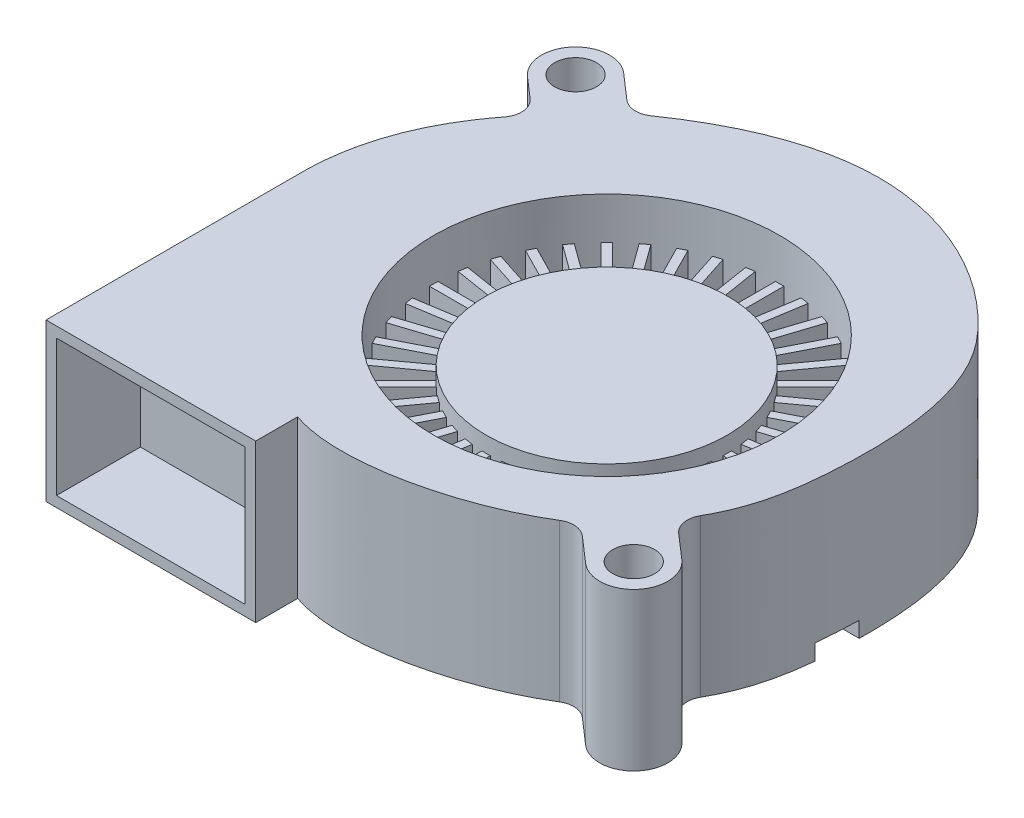
SolidWorks part; units mm, degrees
ref_plane "Front Plane" through (0, 0, 0) normal (0, 0, 1) x (1, 0, 0)
ref_plane "Top Plane" through (0, 0, 0) normal (0, 1, 0) x (1, 0, 0)
ref_plane "Right Plane" through (0, 0, 0) normal (1, 0, 0) x (0, 0, -1)
sketch "Sketch1" plane through (0, 0, 0) normal (0, 1, 0) x (1, 0, 0)
  line L0 (0, 53.1722) -> (0, -73.3303) construction
  line L1 (-85.9264, 74.8353) -> (113.2192, -98.6052) construction
  line L2 (0, 0) -> (35.3553, 35.3553) construction
  line L3 (-92.8119, -25.4688) -> (115.0441, -25.4688) construction
  line L4 (-28, -25.4688) -> (-8, -25.4688)
  line L5 (-8, -25.4688) -> (-8, -21.4688)
  line L6 (-28, -25.4688) -> (-28, -0.4688)
  line L7 (-25.1345, 17.5804) -> (-21.7087, 14.5968)
  line L8 (-27.6468, 14.6958) -> (-16.0044, 28.0636) construction
  line L9 (-20.8655, 22.482) -> (-17.254, 19.3367)
  line L10 (15.2709, -22.8153) -> (26.2326, -10.229) construction
  line L11 (17.8491, -19.855) -> (14.2534, -16.7234)
  line L12 (22.1181, -14.9534) -> (18.496, -11.7988)
  line L13 (5.1229, 26) -> (-4.8978, 26) construction
  circle A0 centre (0, 0) radius 11.5
  circle A1 centre (0, 0) radius 16.5
  circle A2 centre (-23, 20.0312) radius 2
  circle A3 centre (19.9836, -17.4042) radius 2
  arc A4 (-20.8655, 22.482) -> (-25.1345, 17.5804) centre (-23, 20.0312) ccw
  arc A5 (17.8491, -19.855) -> (22.1181, -14.9534) centre (19.9836, -17.4042) ccw
  spline S0 degree 2 poles (-28, -0.4688) (-27.7498, 7.7362) (-21.7087, 14.5968) knots 0 0 0 0.146641 0.146641 0.146641
  spline S1 degree 3 poles (-17.254, 19.3367) (-13.1006, 22.4583) (-6.5843, 25.9822) (5.2341, 26.0653) (12.9163, 22.9052) (21.8609, 13.2015) (22.5883, 0.0872) (21.0626, -8.1071) (18.496, -11.7988) knots 0.198948 0.198948 0.198948 0.198948 0.358848 0.392677 0.521173 0.55031 0.667984 0.765326 0.765326 0.765326 0.765326
  spline S2 degree 3 poles (14.2534, -16.7234) (8.3416, -20.9384) (-2.1416, -23.5492) (-8, -21.4688) knots 0.819888 0.819888 0.819888 0.819888 1 1 1 1
  point P8 (-23, 20.0312)
  point P9 (19.9836, -17.4042)
  point P18 (-19.6066, 17.0758)
  point P21 (0, 26)
  point P22 (16.5902, -14.4488)
  point P23 (17.6777, 17.6777)
  point P25 (0, -22)
  point P27 (22, 0)
  point P32 (-20.8655, 22.482)
  point P36 (-25.1345, 17.5804)
  dimension "D1" = 23
  dimension "D2" = 33
  dimension "D5" = 26.5
  dimension "D11" = 4
  dimension "D19" = 6.5
  dimension "D21" = 6.5
  dimension "D4" = 30.5
  dimension "D7" = 8
  dimension "D8" = 20
  dimension "D9" = 4
  dimension "D10" = 25
  dimension "D12" = 26
  dimension "D13" = 26
  dimension "D14" = 22
  dimension "D15" = 45
  dimension "D16" = 25
  dimension "D17" = 22
  dimension "D18" = 22
  dimension "D22" = 5
  dimension "D23" = 45.5
extrude "Boss-Extrude1" add sketch "Sketch1" along normal blind 15 contours S0 L6 L4 L5 A1 region at (-27.2738, 0, 12.9688)
extrude "Boss-Extrude2" add sketch "Sketch1<3>" along normal blind 12.5 separate body contours A0 region at (0, 0, 0)
sketch "Sketch1<3>" plane through (0, 0, 0) normal (0, 1, 0) x (1, 0, 0) same geometry as "Sketch1"
extrude "Boss-Extrude3" add sketch "Sketch1<4>" along normal blind 7 contours A1 A0 region at (-16.0333, 0, 0)
sketch "Sketch1<4>" plane through (0, 0, 0) normal (0, 1, 0) x (1, 0, 0) same geometry as "Sketch1"
sketch "Sketch2" plane through (0, 7, 0) normal (0, 1, 0) x (1, 0, 0)
  line L0 (-0.4, 11.493) -> (-0.4, 16.4952)
  line L1 (0.4, 16.4952) -> (0.4, 11.493)
  line L4 (0, 16.5) -> (0, 11.5) construction
  line L5 (2.9755, 16.2295) -> (2.193, 11.289)
  line L6 (1.4028, 11.4141) -> (2.1853, 16.3546)
  line L7 (5.4777, 15.5642) -> (3.932, 10.8069)
  line L8 (3.1711, 11.0541) -> (4.7169, 15.8114)
  line L9 (7.845, 14.5157) -> (5.5741, 10.0588)
  line L10 (4.8613, 10.422) -> (7.1322, 14.8789)
  line L11 (10.0192, 13.1097) -> (7.079, 9.063)
  line L12 (6.4318, 9.5332) -> (9.372, 13.58)
  line L13 (11.9467, 11.381) -> (8.4097, 7.844)
  line L14 (7.844, 8.4097) -> (11.381, 11.9467)
  line L15 (13.58, 9.372) -> (9.5332, 6.4318)
  line L16 (9.063, 7.079) -> (13.1097, 10.0192)
  line L17 (14.8789, 7.1322) -> (10.422, 4.8613)
  line L18 (10.0588, 5.5741) -> (14.5157, 7.845)
  line L19 (15.8114, 4.7169) -> (11.0541, 3.1711)
  line L20 (10.8069, 3.932) -> (15.5642, 5.4777)
  line L21 (16.3546, 2.1853) -> (11.4141, 1.4028)
  line L22 (11.289, 2.193) -> (16.2295, 2.9755)
  line L23 (16.4952, -0.4) -> (11.493, -0.4)
  line L24 (11.493, 0.4) -> (16.4952, 0.4)
  line L25 (16.2295, -2.9755) -> (11.289, -2.193)
  line L26 (11.4141, -1.4028) -> (16.3546, -2.1853)
  line L27 (15.5642, -5.4777) -> (10.8069, -3.932)
  line L28 (11.0541, -3.1711) -> (15.8114, -4.7169)
  line L29 (14.5157, -7.845) -> (10.0588, -5.5741)
  line L30 (10.422, -4.8613) -> (14.8789, -7.1322)
  line L31 (13.1097, -10.0192) -> (9.063, -7.079)
  line L32 (9.5332, -6.4318) -> (13.58, -9.372)
  line L33 (11.381, -11.9467) -> (7.844, -8.4097)
  line L34 (8.4097, -7.844) -> (11.9467, -11.381)
  line L35 (9.372, -13.58) -> (6.4318, -9.5332)
  line L36 (7.079, -9.063) -> (10.0192, -13.1097)
  line L37 (7.1322, -14.8789) -> (4.8613, -10.422)
  line L38 (5.5741, -10.0588) -> (7.845, -14.5157)
  line L39 (4.7169, -15.8114) -> (3.1711, -11.0541)
  line L40 (3.932, -10.8069) -> (5.4777, -15.5642)
  line L41 (2.1853, -16.3546) -> (1.4028, -11.4141)
  line L42 (2.193, -11.289) -> (2.9755, -16.2295)
  line L43 (-0.4, -16.4952) -> (-0.4, -11.493)
  line L44 (0.4, -11.493) -> (0.4, -16.4952)
  line L45 (-2.9755, -16.2295) -> (-2.193, -11.289)
  line L46 (-1.4028, -11.4141) -> (-2.1853, -16.3546)
  line L47 (-5.4777, -15.5642) -> (-3.932, -10.8069)
  line L48 (-3.1711, -11.0541) -> (-4.7169, -15.8114)
  line L49 (-7.845, -14.5157) -> (-5.5741, -10.0588)
  line L50 (-4.8613, -10.422) -> (-7.1322, -14.8789)
  line L51 (-10.0192, -13.1097) -> (-7.079, -9.063)
  line L52 (-6.4318, -9.5332) -> (-9.372, -13.58)
  line L53 (-11.9467, -11.381) -> (-8.4097, -7.844)
  line L54 (-7.844, -8.4097) -> (-11.381, -11.9467)
  line L55 (-13.58, -9.372) -> (-9.5332, -6.4318)
  line L56 (-9.063, -7.079) -> (-13.1097, -10.0192)
  line L57 (-14.8789, -7.1322) -> (-10.422, -4.8613)
  line L58 (-10.0588, -5.5741) -> (-14.5157, -7.845)
  line L59 (-15.8114, -4.7169) -> (-11.0541, -3.1711)
  line L60 (-10.8069, -3.932) -> (-15.5642, -5.4777)
  line L61 (-16.3546, -2.1853) -> (-11.4141, -1.4028)
  line L62 (-11.289, -2.193) -> (-16.2295, -2.9755)
  line L63 (-16.4952, 0.4) -> (-11.493, 0.4)
  line L64 (-11.493, -0.4) -> (-16.4952, -0.4)
  line L65 (-16.2295, 2.9755) -> (-11.289, 2.193)
  line L66 (-11.4141, 1.4028) -> (-16.3546, 2.1853)
  line L67 (-15.5642, 5.4777) -> (-10.8069, 3.932)
  line L68 (-11.0541, 3.1711) -> (-15.8114, 4.7169)
  line L69 (-14.5157, 7.845) -> (-10.0588, 5.5741)
  line L70 (-10.422, 4.8613) -> (-14.8789, 7.1322)
  line L71 (-13.1097, 10.0192) -> (-9.063, 7.079)
  line L72 (-9.5332, 6.4318) -> (-13.58, 9.372)
  line L73 (-11.381, 11.9467) -> (-7.844, 8.4097)
  line L74 (-8.4097, 7.844) -> (-11.9467, 11.381)
  line L75 (-9.372, 13.58) -> (-6.4318, 9.5332)
  line L76 (-7.079, 9.063) -> (-10.0192, 13.1097)
  line L77 (-7.1322, 14.8789) -> (-4.8613, 10.422)
  line L78 (-5.5741, 10.0588) -> (-7.845, 14.5157)
  line L79 (-4.7169, 15.8114) -> (-3.1711, 11.0541)
  line L80 (-3.932, 10.8069) -> (-5.4777, 15.5642)
  line L81 (-2.1853, 16.3546) -> (-1.4028, 11.4141)
  line L82 (-2.193, 11.289) -> (-2.9755, 16.2295)
  circle A2 centre (0, 0) radius 16.5 construction
  circle A3 centre (0, 0) radius 11.5 construction
  arc A4 (0.4, 16.4952) -> (-0.4, 16.4952) centre (0, 0) ccw
  arc A5 (0.4, 11.493) -> (-0.4, 11.493) centre (0, 0) ccw
  arc A6 (2.9755, 16.2295) -> (2.1853, 16.3546) centre (0, 0) ccw
  arc A7 (2.193, 11.289) -> (1.4028, 11.4141) centre (0, 0) ccw
  arc A8 (5.4777, 15.5642) -> (4.7169, 15.8114) centre (0, 0) ccw
  arc A9 (3.932, 10.8069) -> (3.1711, 11.0541) centre (0, 0) ccw
  arc A10 (7.845, 14.5157) -> (7.1322, 14.8789) centre (0, 0) ccw
  arc A11 (5.5741, 10.0588) -> (4.8613, 10.422) centre (0, 0) ccw
  arc A12 (10.0192, 13.1097) -> (9.372, 13.58) centre (0, 0) ccw
  arc A13 (7.079, 9.063) -> (6.4318, 9.5332) centre (0, 0) ccw
  arc A14 (11.9467, 11.381) -> (11.381, 11.9467) centre (0, 0) ccw
  arc A15 (8.4097, 7.844) -> (7.844, 8.4097) centre (0, 0) ccw
  arc A16 (13.58, 9.372) -> (13.1097, 10.0192) centre (0, 0) ccw
  arc A17 (9.5332, 6.4318) -> (9.063, 7.079) centre (0, 0) ccw
  arc A18 (14.8789, 7.1322) -> (14.5157, 7.845) centre (0, 0) ccw
  arc A19 (10.422, 4.8613) -> (10.0588, 5.5741) centre (0, 0) ccw
  arc A20 (15.8114, 4.7169) -> (15.5642, 5.4777) centre (0, 0) ccw
  arc A21 (11.0541, 3.1711) -> (10.8069, 3.932) centre (0, 0) ccw
  arc A22 (16.3546, 2.1853) -> (16.2295, 2.9755) centre (0, 0) ccw
  arc A23 (11.4141, 1.4028) -> (11.289, 2.193) centre (0, 0) ccw
  arc A24 (16.4952, -0.4) -> (16.4952, 0.4) centre (0, 0) ccw
  arc A25 (11.493, -0.4) -> (11.493, 0.4) centre (0, 0) ccw
  arc A26 (16.2295, -2.9755) -> (16.3546, -2.1853) centre (0, 0) ccw
  arc A27 (11.289, -2.193) -> (11.4141, -1.4028) centre (0, 0) ccw
  arc A28 (15.5642, -5.4777) -> (15.8114, -4.7169) centre (0, 0) ccw
  arc A29 (10.8069, -3.932) -> (11.0541, -3.1711) centre (0, 0) ccw
  arc A30 (14.5157, -7.845) -> (14.8789, -7.1322) centre (0, 0) ccw
  arc A31 (10.0588, -5.5741) -> (10.422, -4.8613) centre (0, 0) ccw
  arc A32 (13.1097, -10.0192) -> (13.58, -9.372) centre (0, 0) ccw
  arc A33 (9.063, -7.079) -> (9.5332, -6.4318) centre (0, 0) ccw
  arc A34 (11.381, -11.9467) -> (11.9467, -11.381) centre (0, 0) ccw
  arc A35 (7.844, -8.4097) -> (8.4097, -7.844) centre (0, 0) ccw
  arc A36 (9.372, -13.58) -> (10.0192, -13.1097) centre (0, 0) ccw
  arc A37 (6.4318, -9.5332) -> (7.079, -9.063) centre (0, 0) ccw
  arc A38 (7.1322, -14.8789) -> (7.845, -14.5157) centre (0, 0) ccw
  arc A39 (4.8613, -10.422) -> (5.5741, -10.0588) centre (0, 0) ccw
  arc A40 (4.7169, -15.8114) -> (5.4777, -15.5642) centre (0, 0) ccw
  arc A41 (3.1711, -11.0541) -> (3.932, -10.8069) centre (0, 0) ccw
  arc A42 (2.1853, -16.3546) -> (2.9755, -16.2295) centre (0, 0) ccw
  arc A43 (1.4028, -11.4141) -> (2.193, -11.289) centre (0, 0) ccw
  arc A44 (-0.4, -16.4952) -> (0.4, -16.4952) centre (0, 0) ccw
  arc A45 (-0.4, -11.493) -> (0.4, -11.493) centre (0, 0) ccw
  arc A46 (-2.9755, -16.2295) -> (-2.1853, -16.3546) centre (0, 0) ccw
  arc A47 (-2.193, -11.289) -> (-1.4028, -11.4141) centre (0, 0) ccw
  arc A48 (-5.4777, -15.5642) -> (-4.7169, -15.8114) centre (0, 0) ccw
  arc A49 (-3.932, -10.8069) -> (-3.1711, -11.0541) centre (0, 0) ccw
  arc A50 (-7.845, -14.5157) -> (-7.1322, -14.8789) centre (0, 0) ccw
  arc A51 (-5.5741, -10.0588) -> (-4.8613, -10.422) centre (0, 0) ccw
  arc A52 (-10.0192, -13.1097) -> (-9.372, -13.58) centre (0, 0) ccw
  arc A53 (-7.079, -9.063) -> (-6.4318, -9.5332) centre (0, 0) ccw
  arc A54 (-11.9467, -11.381) -> (-11.381, -11.9467) centre (0, 0) ccw
  arc A55 (-8.4097, -7.844) -> (-7.844, -8.4097) centre (0, 0) ccw
  arc A56 (-13.58, -9.372) -> (-13.1097, -10.0192) centre (0, 0) ccw
  arc A57 (-9.5332, -6.4318) -> (-9.063, -7.079) centre (0, 0) ccw
  arc A58 (-14.8789, -7.1322) -> (-14.5157, -7.845) centre (0, 0) ccw
  arc A59 (-10.422, -4.8613) -> (-10.0588, -5.5741) centre (0, 0) ccw
  arc A60 (-15.8114, -4.7169) -> (-15.5642, -5.4777) centre (0, 0) ccw
  arc A61 (-11.0541, -3.1711) -> (-10.8069, -3.932) centre (0, 0) ccw
  arc A62 (-16.3546, -2.1853) -> (-16.2295, -2.9755) centre (0, 0) ccw
  arc A63 (-11.4141, -1.4028) -> (-11.289, -2.193) centre (0, 0) ccw
  arc A64 (-16.4952, 0.4) -> (-16.4952, -0.4) centre (0, 0) ccw
  arc A65 (-11.493, 0.4) -> (-11.493, -0.4) centre (0, 0) ccw
  arc A66 (-16.2295, 2.9755) -> (-16.3546, 2.1853) centre (0, 0) ccw
  arc A67 (-11.289, 2.193) -> (-11.4141, 1.4028) centre (0, 0) ccw
  arc A68 (-15.5642, 5.4777) -> (-15.8114, 4.7169) centre (0, 0) ccw
  arc A69 (-10.8069, 3.932) -> (-11.0541, 3.1711) centre (0, 0) ccw
  arc A70 (-14.5157, 7.845) -> (-14.8789, 7.1322) centre (0, 0) ccw
  arc A71 (-10.0588, 5.5741) -> (-10.422, 4.8613) centre (0, 0) ccw
  arc A72 (-13.1097, 10.0192) -> (-13.58, 9.372) centre (0, 0) ccw
  arc A73 (-9.063, 7.079) -> (-9.5332, 6.4318) centre (0, 0) ccw
  arc A74 (-11.381, 11.9467) -> (-11.9467, 11.381) centre (0, 0) ccw
  arc A75 (-7.844, 8.4097) -> (-8.4097, 7.844) centre (0, 0) ccw
  arc A76 (-9.372, 13.58) -> (-10.0192, 13.1097) centre (0, 0) ccw
  arc A77 (-6.4318, 9.5332) -> (-7.079, 9.063) centre (0, 0) ccw
  arc A78 (-7.1322, 14.8789) -> (-7.845, 14.5157) centre (0, 0) ccw
  arc A79 (-4.8613, 10.422) -> (-5.5741, 10.0588) centre (0, 0) ccw
  arc A80 (-4.7169, 15.8114) -> (-5.4777, 15.5642) centre (0, 0) ccw
  arc A81 (-3.1711, 11.0541) -> (-3.932, 10.8069) centre (0, 0) ccw
  arc A82 (-2.1853, 16.3546) -> (-2.9755, 16.2295) centre (0, 0) ccw
  arc A83 (-1.4028, 11.4141) -> (-2.193, 11.289) centre (0, 0) ccw
  point P167 (0, 0)
  dimension "D1" = 0.8
  dimension "D2" = 40
extrude "Boss-Extrude4" add sketch "Sketch2" along normal blind 4
sketch "Sketch3" plane through (0, 0, 25.4688) normal (0, 0, 1) x (1, 0, 0)
  line L0 (-28, 15) -> (-8, 15) construction
  line L1 (-28, 15) -> (-28, 0) construction
  line L2 (-28, 0) -> (-8, 0) construction
  line L3 (-8, 15) -> (-8, 0) construction
  line L4 (-28, 15) -> (-8, 15) construction
  line L5 (-28, 15) -> (-28, 0) construction
  line L6 (-28, 0) -> (-8, 0) construction
  line L7 (-8, 15) -> (-8, 0) construction
  line L8 (-27, 14) -> (-9, 14)
  line L9 (-9, 14) -> (-9, 1)
  line L10 (-27, 1) -> (-9, 1)
  line L11 (-27, 14) -> (-27, 1)
  dimension "D1" = 1
extrude "Cut-Extrude1" cut sketch "Sketch3" against normal blind 8
sketch "Sketch4" plane through (0, 0, 0) normal (0, -1, 0) x (1, 0, 0)
  line L0 (21.8481, 1.9964) -> (16.8481, 2)
  line L1 (16.8481, 2) -> (16.8452, -2)
  line L2 (16.8452, -2) -> (22.0767, -2.0038)
  line L3 (16.8466, 0) -> (22.6576, 0) construction
  line L4 (0, 0) -> (10.7358, 0) construction
  line L5 (10.7358, 0) -> (16.8466, 0) construction
  spline S0 degree 3 poles (478.231, -887.9477) (-72.0672, 162.1216) (-51.6688, -25.6655) (5.2341, -26.0653) (12.9163, -22.9052) (21.8609, -13.2015) (24.7275, 38.4806) (-13.2848, 25.4207) (-919.1441, 359.3539) knots -1.030267 -1.030267 -1.030267 -1.030267 0.358848 0.392677 0.521173 0.55031 0.667984 1.48335 1.48335 1.48335 1.48335 only from (-17.254, -19.3367) to (18.496, 11.7988) construction
  spline S1 degree 3 poles (22.0767, -2.0038) (22.0636, -1.324) (22.0087, 0.0426) (21.9129, 1.3458) (21.8481, 1.9964) knots 0.653497 0.653497 0.653497 0.653497 0.667984 0.683061 0.683061 0.683061 0.683061
  point P9 (22.1354, -3.0162)
  dimension "D1" = 4
  dimension "D2" = 5
extrude "Cut-Extrude2" cut sketch "Sketch4" against normal blind 1.5
fillet "Fillet1" radius 2 4 edges at (14.2534, 7.5, 16.7234) (18.496, 7.5, 11.7988) (-17.254, 7.5, -19.3367) (-21.7087, 7.5, -14.5968)
